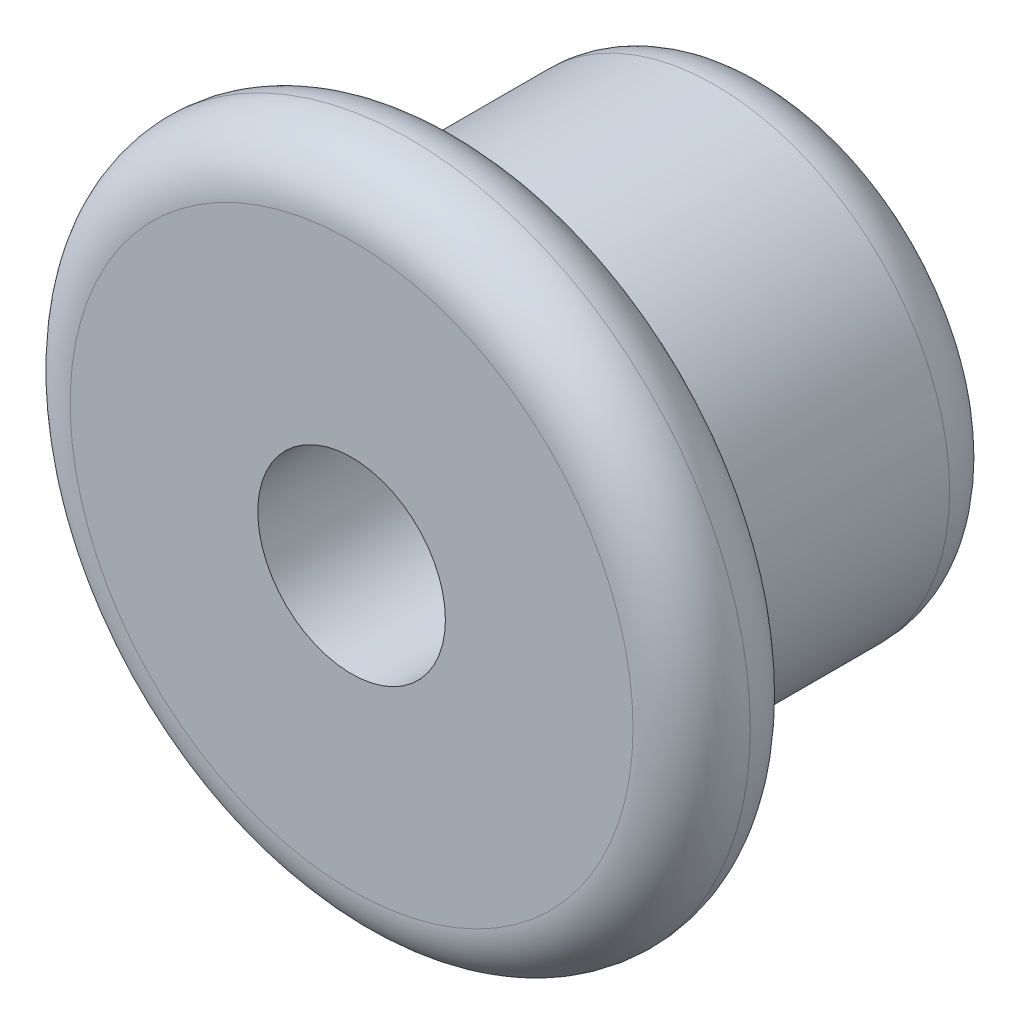
SolidWorks part; units mm, degrees
material "陶瓷"
ref_plane "前视基准面" through (0, 0, 0) normal (0, 0, 1) x (1, 0, 0)
ref_plane "上视基准面" through (0, 0, 0) normal (0, 1, 0) x (1, 0, 0)
ref_plane "右视基准面" through (0, 0, 0) normal (1, 0, 0) x (0, 0, -1)
sketch "草图1" plane through (0, 0, 0) normal (0, 0, 1) x (1, 0, 0)
  circle A0 centre (0, 0) radius 2
  dimension "D1" = 4
extrude "凸台-拉伸1" add sketch "草图1" along normal blind 2.6
sketch "草图2" plane through (0, 0, 2.6) normal (0, 0, 1) x (1, 0, 0)
  circle A0 centre (0, 0) radius 2.9
  dimension "D1" = 5.8
extrude "凸台-拉伸2" add sketch "草图2" along normal blind 1
sketch "草图3" plane through (0, 0, 3.6) normal (0, 0, 1) x (1, 0, 0)
  circle A0 centre (0, 0) radius 0.8
  dimension "D1" = 1.6
extrude "切除-拉伸1" cut sketch "草图3" against normal through all both and the other way through all
fillet "圆角2" radius 0.5 3 edges at (2, 0, 0) (2.9, 0, 2.6) (2.9, 0, 3.6)
